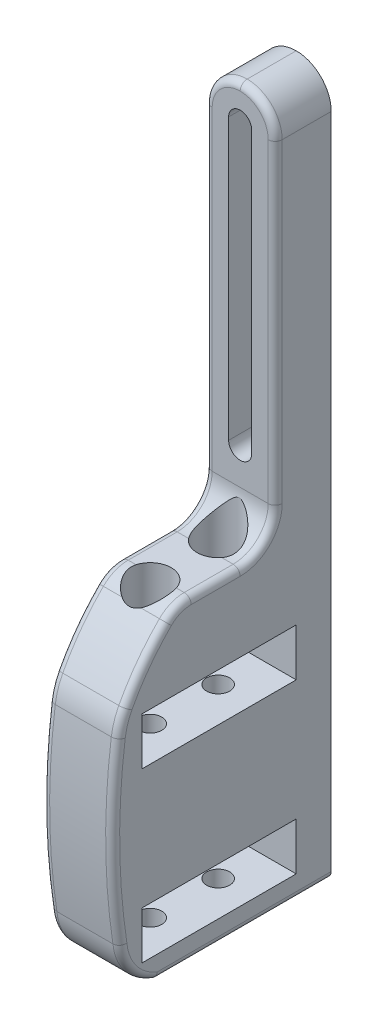
SolidWorks part; units mm, degrees
ref_plane "Front Plane" through (0, 0, 0) normal (0, 0, 1) x (1, 0, 0)
ref_plane "Top Plane" through (0, 0, 0) normal (0, 1, 0) x (1, 0, 0)
ref_plane "Right Plane" through (0, 0, 0) normal (1, 0, 0) x (0, 0, -1)
sketch "Sketch1" plane through (0, 0, 0) normal (0, 0, 1) x (1, 0, 0)
  line L1 (5, 50) -> (-5, 50)
  line L2 (5, 50) -> (5, -50)
  line L3 (5, -50) -> (-5, -50)
  line L4 (-5, 50) -> (-5, -50)
  line L5 (5, 50) -> (-5, -50) construction
  line L6 (5, -50) -> (-5, 50) construction
  point P0 (0, 0)
  dimension "D1" = 10
  dimension "D2" = 100
extrude "Boss-Extrude1" add sketch "Sketch1" along normal blind 25
sketch "Sketch2" plane through (5, 0, 0) normal (1, 0, 0) x (0, 0, -1)
  line L0 (-25, 50) -> (-8, 50)
  line L2 (-25, 50) -> (0, 50) construction
  line L3 (-25, 50) -> (-25, -5)
  line L4 (-25, -50) -> (-25, 50) construction
  line L5 (-25, -5) -> (-8, -5)
  line L6 (-8, -5) -> (-8, 50)
  dimension "D1" = 8
  dimension "D2" = 55
extrude "Cut-Extrude1" cut sketch "Sketch2" against normal blind 25
fillet "Fillet1" radius 5 2 edges at (-5, 50, 4) (5, 50, 4)
fillet "Fillet2" radius 5 2 edges at (0, -5, 25) (0, -5, 8)
sketch "Sketch3" plane through (0, 0, 8) normal (0, 0, 1) x (1, 0, 0)
  line L0 (0, 45) -> (0, 5) construction
  line L1 (1.65, 45) -> (1.65, 5)
  line L2 (-1.65, 45) -> (-1.65, 5)
  arc A0 (1.65, 45) -> (-1.65, 45) centre (0, 45) ccw
  arc A1 (-1.65, 5) -> (1.65, 5) centre (0, 5) ccw
  point P2 (0, 25)
  dimension "D1" = 3.3
  dimension "D2" = 0
  dimension "D3" = 5
extrude "Cut-Extrude2" cut sketch "Sketch3" against normal blind 8
sketch "Sketch4" plane through (5, 0, 0) normal (1, 0, 0) x (0, 0, -1)
  line L0 (0, -50) -> (0, 45) construction
  line L1 (-5, -16) -> (-27, -16)
  line L2 (-5, -16) -> (-5, -22.8)
  line L3 (-5, -22.8) -> (-27, -22.8)
  line L4 (-27, -16) -> (-27, -22.8)
  line L5 (-20, -5) -> (-13, -5) construction
  line L7 (-27, -40) -> (-5, -40)
  line L8 (-27, -40) -> (-27, -46.8)
  line L9 (-27, -46.8) -> (-5, -46.8)
  line L10 (-5, -40) -> (-5, -46.8)
  dimension "D1" = 22
  dimension "D2" = 5
  dimension "D3" = 11
  dimension "D4" = 6.8
  dimension "D5" = 6.8
  dimension "D6" = 22
  dimension "D7" = 5
  dimension "D8" = 35
extrude "Cut-Extrude3" cut sketch "Sketch4" against normal blind 10
sketch "Sketch5" plane through (5, 0, 0) normal (1, 0, 0) x (0, 0, -1)
  line L0 (-27, -16) -> (-25, -16)
  line L1 (-27, -16) -> (-27, -22.8)
  line L2 (-27, -22.8) -> (-25, -22.8)
  line L4 (-25, -40) -> (-27, -40)
  line L5 (-27, -40) -> (-27, -46.8)
  line L6 (-27, -46.8) -> (-25, -46.8)
  line L7 (-25, -22.8) -> (-25, -40)
  line L8 (-23.5355, -6.4645) -> (-25, -16)
  line L9 (-25, -46.8) -> (-25, -50)
  arc A0 (-23.5355, -6.4645) -> (-29.3388, -14.3036) centre (-0.6683, -29.4606) ccw
  arc A1 (-20, -5) -> (-25, -10) centre (-20, -10) ccw construction
  arc A2 (-25, -50) -> (-30.1733, -43.3769) centre (-22.4175, -42.6508) cw
  arc A3 (-30.4097, -17.65) -> (-30.1733, -43.3769) centre (59.488, -29.6884) ccw
  arc A4 (-29.3388, -14.3036) -> (-30.4097, -17.65) centre (-20.4982, -18.9773) ccw
  dimension "D2" = 10
extrude "Boss-Extrude2" add sketch "Sketch5" against normal blind 10
fillet "Fillet3" radius 1 20 edges at (5, -30.5219, 31.2083) (5, -15.9294, 30.0224) (5, -10.1646, 26.7336) (5, -5.3806, 21.9134) (5, -5, 16.5) (5, -3.5355, 9.4645) (-5, -30.5219, 31.2083) (-5, -15.9294, 30.0224) (-5, -10.1646, 26.7336) (-5, -5.3806, 21.9134) (-5, -5, 16.5) (-5, -3.5355, 9.4645) (-5, 22.5, 8) (-3.5355, 48.5355, 8) (3.5355, 48.5355, 8) (-5, -50, 12.5) (5, -50, 12.5) (-5, -47.4459, 28.5564) (5, -47.4459, 28.5564) (5, 22.5, 8)
sketch "Sketch6" plane through (0, -22.8, 0) normal (0, 1, 0) x (1, 0, 0)
  circle A0 centre (0, -11.15) radius 1.65
  circle A1 centre (0, -20.85) radius 1.65
  point P9 (0, -16)
  dimension "D2" = 3.3
  dimension "D3" = 3.3
  dimension "D1" = 9.7
extrude "Cut-Extrude4" cut sketch "Sketch6" against normal blind 30 and the other way blind 20
sketch "Sketch7" plane through (0, -5, 0) normal (0, 1, 0) x (1, 0, 0)
  circle A0 centre (0, -20.85) radius 3
  circle A1 centre (0, -11.15) radius 3
  dimension "D1" = 6
  dimension "D2" = 6
extrude "Cut-Extrude5" cut sketch "Sketch7" against normal blind 7 and the other way blind 10
